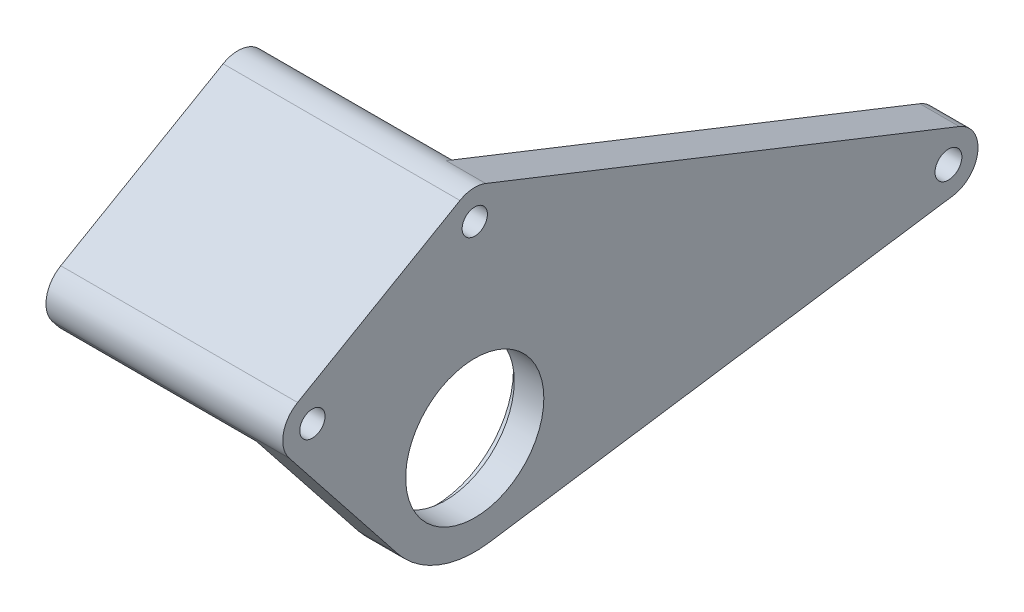
SolidWorks part; units mm, degrees
ref_plane "Front Plane" through (0, 0, 0) normal (0, 0, 1) x (1, 0, 0)
ref_plane "Top Plane" through (0, 0, 0) normal (0, 1, 0) x (1, 0, 0)
ref_plane "Right Plane" through (0, 0, 0) normal (1, 0, 0) x (0, 0, -1)
sketch "Sketch1" plane through (0, 0, 0) normal (1, 0, 0) x (0, 0, -1)
  line L0 (1.7528, 4.4282) -> (-74.4472, 34.5907)
  line L1 (-78.5812, 34.2869) -> (-104.7027, 19.2057)
  line L2 (-106.0548, 12.1242) -> (-88.6443, -9.8568)
  line L3 (-73.8849, -15.7053) -> (0.6945, -4.7116)
  line L4 (-102.3215, 15.0813) -> (-76.2, 0) construction
  line L5 (-76.2, 0) -> (-76.2, 30.1625) construction
  line L6 (0, 0) -> (-76.2, 0) construction
  circle A0 centre (0, 0) radius 2.159
  arc A1 (0.6945, -4.7116) -> (1.7528, 4.4282) centre (0, 0) ccw
  arc A2 (-74.4472, 34.5907) -> (-78.5812, 34.2869) centre (-76.2, 30.1625) ccw
  arc A3 (-104.7027, 19.2057) -> (-106.0548, 12.1242) centre (-102.3215, 15.0813) ccw
  arc A4 (-88.6443, -9.8568) -> (-73.8849, -15.7053) centre (-76.2, 0) ccw
  circle A5 centre (-76.2, 0) radius 11.1125
  circle A6 centre (-76.2, 30.1625) radius 2.032
  circle A7 centre (-76.2, 0) radius 26.1938 construction
  circle A8 centre (-102.3215, 15.0813) radius 2.032
  dimension "D1" = 4.318
  dimension "D2" = 9.525
  dimension "D3" = 22.225
  dimension "D4" = 4.7625
  dimension "D5" = 15.875
  dimension "D6" = 52.3875
  dimension "D10" = 4.064
  dimension "D7" = 30.1625
  dimension "D8" = 76.2
  dimension "D9" = 60
extrude "Boss-Extrude1" add sketch "Sketch1" along normal blind 6.35
sketch "Sketch2" plane through (6.35, 0, 0) normal (1, 0, 0) x (0, 0, -1)
  circle A0 centre (-76.2, 0) radius 12.573
  dimension "D1" = 25.146
extrude "Cut-Extrude1" cut sketch "Sketch2" against normal blind 1.5875
sketch "Sketch3" plane through (6.35, 0, 0) normal (1, 0, 0) x (0, 0, -1)
  line L1 (-76.2, 33.902) -> (-79.4385, 32.0322)
  line L2 (-79.4385, 32.0322) -> (-79.4385, 28.2928)
  line L3 (-79.4385, 28.2928) -> (-76.2, 26.423)
  line L4 (-76.2, 26.423) -> (-72.9615, 28.2928)
  line L5 (-72.9615, 28.2928) -> (-72.9615, 32.0322)
  line L6 (-72.9615, 32.0322) -> (-76.2, 33.902)
  line L7 (-102.3215, 18.8207) -> (-105.56, 16.951)
  line L8 (-105.56, 16.951) -> (-105.56, 13.2115)
  line L9 (-105.56, 13.2115) -> (-102.3215, 11.3418)
  line L10 (-102.3215, 11.3418) -> (-99.083, 13.2115)
  line L11 (-99.083, 13.2115) -> (-99.083, 16.951)
  line L12 (-99.083, 16.951) -> (-102.3215, 18.8207)
  line L13 (-78.5813, 34.2869) -> (-104.7027, 19.2057)
  line L14 (-106.0548, 12.1242) -> (-101.5807, 6.4756)
  line L16 (-71.4639, 30.6634) -> (-71.374, 29.2453)
  line L17 (1.5302, 4.51) -> (-87.3698, 34.6725) construction
  line L18 (-71.374, 25.7453) -> (-71.374, 29.2453)
  line L20 (-78.5812, 34.2869) -> (-104.7027, 19.2057) construction
  line L21 (-106.0548, 12.1242) -> (-88.6443, -9.8568) construction
  circle A0 centre (-76.2, 30.1625) radius 3.2385 construction
  circle A1 centre (-102.3215, 15.0813) radius 3.2385 construction
  arc A4 (-71.4639, 30.6634) -> (-78.5813, 34.2869) centre (-76.2, 30.1625) ccw
  arc A5 (-104.7027, 19.2057) -> (-106.0548, 12.1242) centre (-102.3215, 15.0813) ccw
  arc A6 (-101.5807, 6.4756) -> (-71.374, 25.7453) centre (-76.2, 0) cw
  arc A7 (-74.4472, 34.5907) -> (-78.5812, 34.2869) centre (-76.2, 30.1625) ccw construction
  arc A8 (-104.7027, 19.2057) -> (-106.0548, 12.1242) centre (-102.3215, 15.0813) ccw construction
  point P0 (-71.374, 30.6634)
  point P9 (-88.9, 29.6498)
  dimension "D4" = 26.1937
  dimension "D1" = 6.477
  dimension "D2" = 6.477
  dimension "D3" = 1.5875
extrude "Boss-Extrude2" add sketch "Sketch3" along normal blind 31.75
fillet "Fillet1" radius 3.175 2 edges at (22.225, 25.7453, 71.374) (22.225, 6.4756, 101.5807)
mirror "Mirror1" about plane through (6.35, 0, 0) normal (1, 0, 0) of bodies 104 102
delete or keep bodies "Body-Delete/Keep 1" type delete bodies bodies 104
